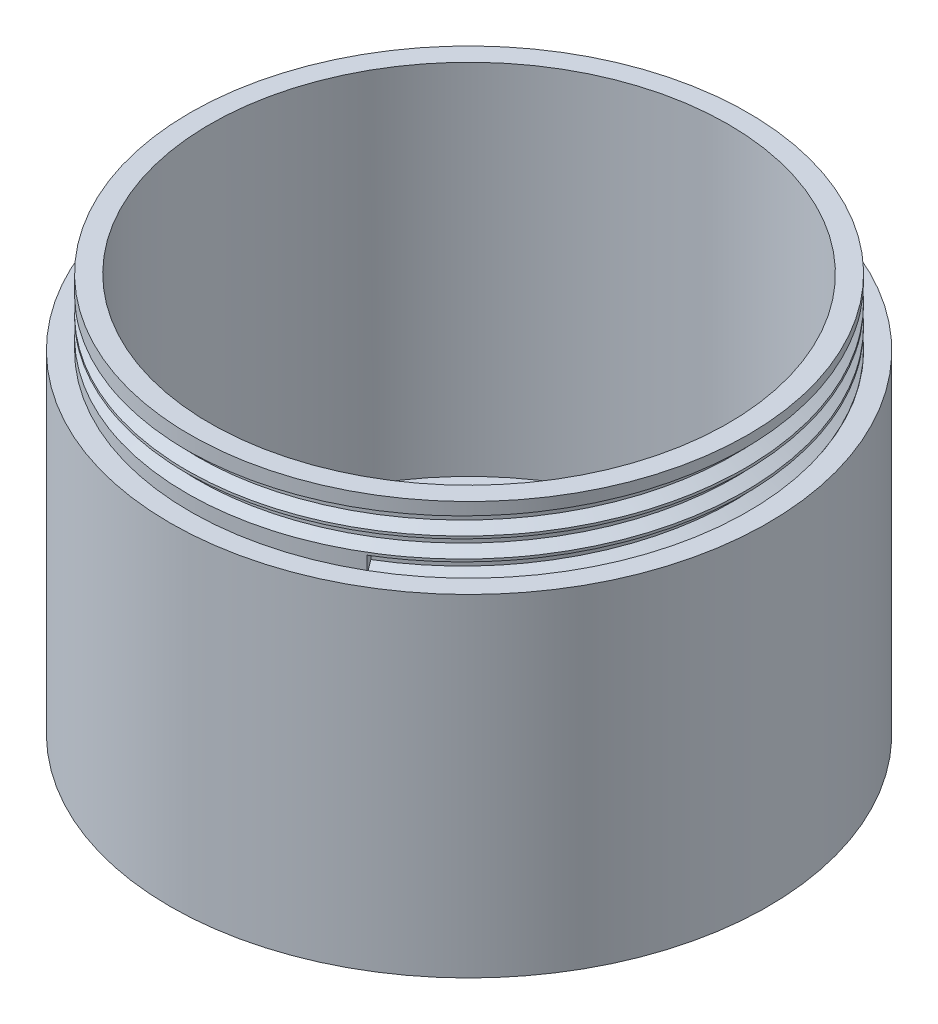
SolidWorks part; units mm, degrees
ref_plane "Front Plane" through (0, 0, 0) normal (0, 0, 1) x (1, 0, 0)
ref_plane "Top Plane" through (0, 0, 0) normal (0, 1, 0) x (1, 0, 0)
ref_plane "Right Plane" through (0, 0, 0) normal (1, 0, 0) x (0, 0, -1)
sketch "Sketch1" plane through (0, 0, 0) normal (0, 1, 0) x (1, 0, 0)
  circle A0 centre (0, 0) radius 45
  dimension "D1" = 90
extrude "Boss-Extrude1" add sketch "Sketch1" along normal blind 50
shell "Shell1" thickness 6 removed face at (0, 50, 45)
sketch "Sketch3" plane through (0, 0, 0) normal (0, 0, 1) x (1, 0, 0)
  line L0 (0, 0) -> (0, 60) construction
  line L1 (-39, 50) -> (-42, 50)
  line L2 (-39, 50) -> (-39, 60)
  line L3 (-39, 60) -> (-42, 60)
  line L4 (-42, 50) -> (-42, 60)
  dimension "D1" = 3
  dimension "D2" = 10
revolve "Revolve1" add sketch "Sketch3" angle 360 about L0
thread "Thread1" pitch 3 method cut profile "Thread Profile1" start angle 0, offset 0, length 8, pitch 3, diameter 84
ref_plane "Plane1" through (-42, 60, 0) normal (0, 0, 1) x (-1, 0, 0)
sketch "Thread Profile1" plane through (-42, 60, 0) normal (0, 0, 1) x (-1, 0, 0)
  line L0 (0, 0) -> (0, 3) construction
  line L11 (0, 0) -> (0, 2.625)
  line L12 (0, 2.625) -> (-1.6238, 1.6875)
  line L13 (-1.6238, 1.6875) -> (-1.6238, 0.9375)
  line L15 (-1.6238, 0.9375) -> (0, 0)
  line L17 (-1.6238, 1.3125) -> (0, 1.3125) construction
  point P2 (0, 0)
  dimension "Pitch" = 3
  dimension "Profile_Angle" = 60
  dimension "Profile_Land" = 0.75
  dimension "Profile_Height" = 1.6238
